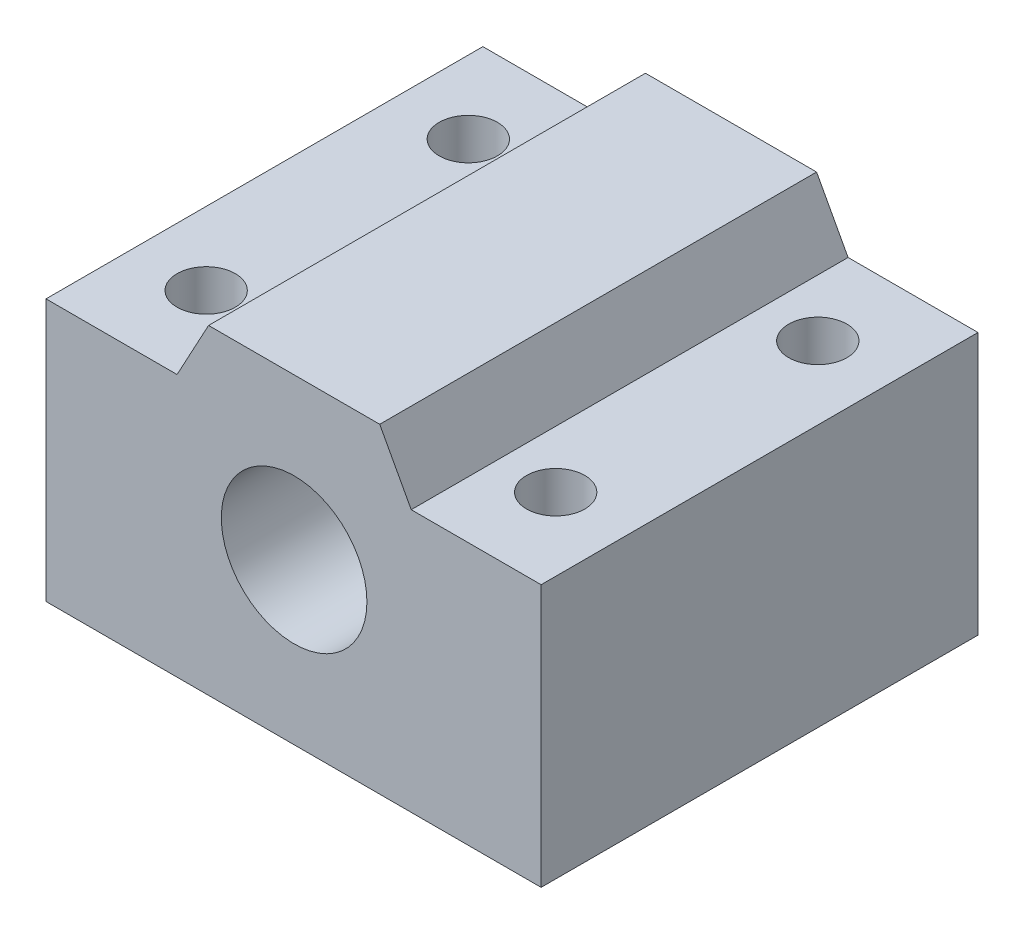
SolidWorks part; units mm, degrees
ref_plane "Front Plane" through (0, 0, 0) normal (0, 0, 1) x (1, 0, 0)
ref_plane "Top Plane" through (0, 0, 0) normal (0, 1, 0) x (1, 0, 0)
ref_plane "Right Plane" through (0, 0, 0) normal (1, 0, 0) x (0, 0, -1)
sketch "body" plane through (0, 0, 0) normal (0, 0, 1) x (1, 0, 0)
  line L0 (-8.0385, 7.0005) -> (-5.8756, 11.0006)
  line L1 (-17.0385, 7.0005) -> (-8.0385, 7.0005)
  line L2 (-17.0385, 7.0005) -> (-17.0385, -10.9994)
  line L3 (-17.0385, -10.9994) -> (16.9615, -10.9994)
  line L4 (16.9615, 7.0005) -> (16.9615, -10.9994)
  line L5 (8.0405, 7.0005) -> (16.9615, 7.0005)
  line L6 (-5.8756, 11.0006) -> (5.8776, 11.0006)
  line L7 (5.8776, 11.0006) -> (8.0405, 7.0005)
  dimension "D1" = 22
  dimension "D2" = 10.9994
  dimension "D3" = 34
sketch "hole" plane through (0, 0, 0) normal (0, 0, 1) x (1, 0, 0)
  circle A0 centre (0, 0) radius 5
extrude "Boss-Extrude2" add sketch "body" against normal blind 30
extrude "Cut-Extrude1" cut sketch "hole" against normal blind 30
sketch "mount hole" plane through (0, 0, 0) normal (0, 1, 0) x (1, 0, 0)
  line L0 (-17.0385, 30) -> (-17.0385, 0) construction
  line L2 (-17.0385, 0) -> (16.9615, 0) construction
  circle A0 centre (-12.0385, 6) radius 2
  circle A1 centre (11.9615, 6) radius 2
  circle A2 centre (11.9615, 24) radius 2
  circle A3 centre (-12.0385, 24) radius 2
  dimension "D1" = 4
  dimension "D4" = 24
  dimension "D2" = 2
  dimension "D3" = 2
  dimension "D5" = 18
  dimension "D6" = 5
  dimension "D7" = 6
extrude "Cut-Extrude2" cut sketch "mount hole" against normal mid plane 30
